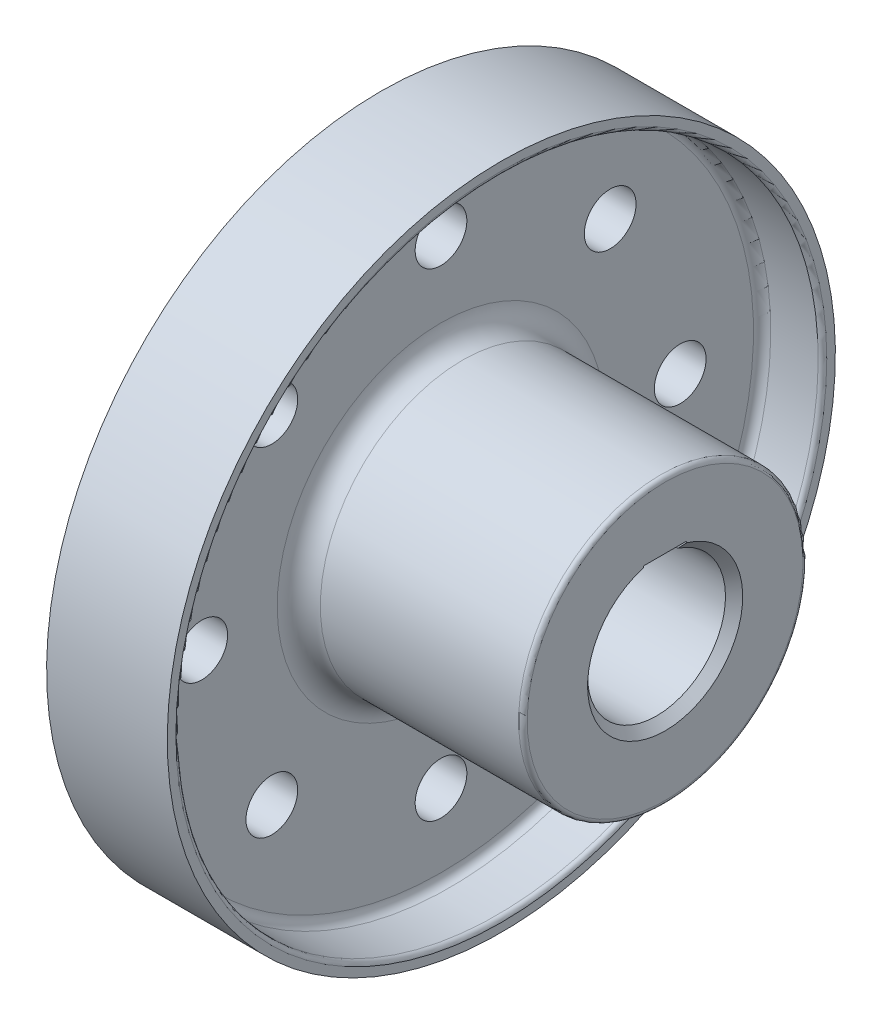
SolidWorks part; units mm, degrees
ref_plane "Front Plane" through (0, 0, 0) normal (0, 0, 1) x (1, 0, 0)
ref_plane "Top Plane" through (0, 0, 0) normal (0, 1, 0) x (1, 0, 0)
ref_plane "Right Plane" through (0, 0, 0) normal (1, 0, 0) x (0, 0, -1)
sketch "Sketch1" plane through (0, 0, 0) normal (0, 0, 1) x (1, 0, 0)
  line L0 (7.1916, 0) -> (-58.8084, 0) construction
  line L1 (7.1916, 0) -> (7.1916, 33)
  line L2 (7.1916, 33) -> (-44.8084, 33)
  line L3 (-44.8084, 33) -> (-44.8084, 74.5)
  line L4 (-44.8084, 74.5) -> (-30.8084, 74.5)
  line L5 (-30.8084, 74.5) -> (-30.8084, 77.5)
  line L6 (-30.8084, 77.5) -> (-58.8084, 77.5)
  line L7 (-58.8084, 77.5) -> (-58.8084, 0)
  line L8 (-58.8084, 0) -> (7.1916, 0)
  dimension "D1" = 77.5
  dimension "D2" = 33
  dimension "D3" = 3
  dimension "D4" = 14
  dimension "D5" = 28
  dimension "D6" = 38
revolve "Revolve1" add sketch "Sketch1" angle 360 about L0
sketch "Sketch2" plane through (-58.8084, 0, 0) normal (-1, 0, 0) x (0, 0, 1)
  circle A0 centre (0, 0) radius 27.5
  dimension "D1" = 55
extrude "Cut-Extrude1" cut sketch "Sketch2" against normal blind 6
sketch "Sketch3" plane through (-52.8084, 0, 0) normal (-1, 0, 0) x (0, 0, 1)
  line L1 (-5, 17.65) -> (5, 17.65)
  line L2 (-5, 17.65) -> (-5, 14.35)
  line L3 (-5, 14.35) -> (5, 14.35)
  line L4 (5, 17.65) -> (5, 14.35)
  line L5 (-5, 17.65) -> (5, 14.35) construction
  line L6 (-5, 14.35) -> (5, 17.65) construction
  circle A0 centre (0, 0) radius 16
  point P3 (0, 16)
  dimension "D1" = 32
  dimension "D2" = 10
  dimension "D3" = 17.65
extrude "Cut-Extrude2" cut sketch "Sketch3" against normal through all contours L2 A0 L4 L3 | L2 L3 L4 L1 region at (-52.8084, -0.2641, 0)
chamfer "Chamfer1" distance 2 angle 45 1 edges at (7.1916, -16, 0)
fillet "Fillet1" radius 1 2 edges at (-30.8084, 74.5, 0) (7.1916, 33, 0)
fillet "Fillet2" radius 2 1 edges at (-44.8084, 74.5, 0)
fillet "Fillet3" radius 5 1 edges at (-44.8084, 33, 0)
sketch "Sketch4" plane through (-58.8084, 0, 0) normal (-1, 0, 0) x (0, 0, 1)
  line L0 (0, 0) -> (0, 109.3895) construction
  circle A0 centre (0, 55.5) radius 6
  circle A1 centre (39.2444, 39.2444) radius 6
  circle A2 centre (55.5, 0) radius 6
  circle A3 centre (39.2444, -39.2444) radius 6
  circle A4 centre (0, -55.5) radius 6
  circle A5 centre (-39.2444, -39.2444) radius 6
  circle A6 centre (-55.5, 0) radius 6
  circle A7 centre (-39.2444, 39.2444) radius 6
  point P21 (0, 0)
  dimension "D1" = 12
  dimension "D2" = 55.5
  dimension "D3" = 8
extrude "Cut-Extrude3" cut sketch "Sketch4" against normal through all
